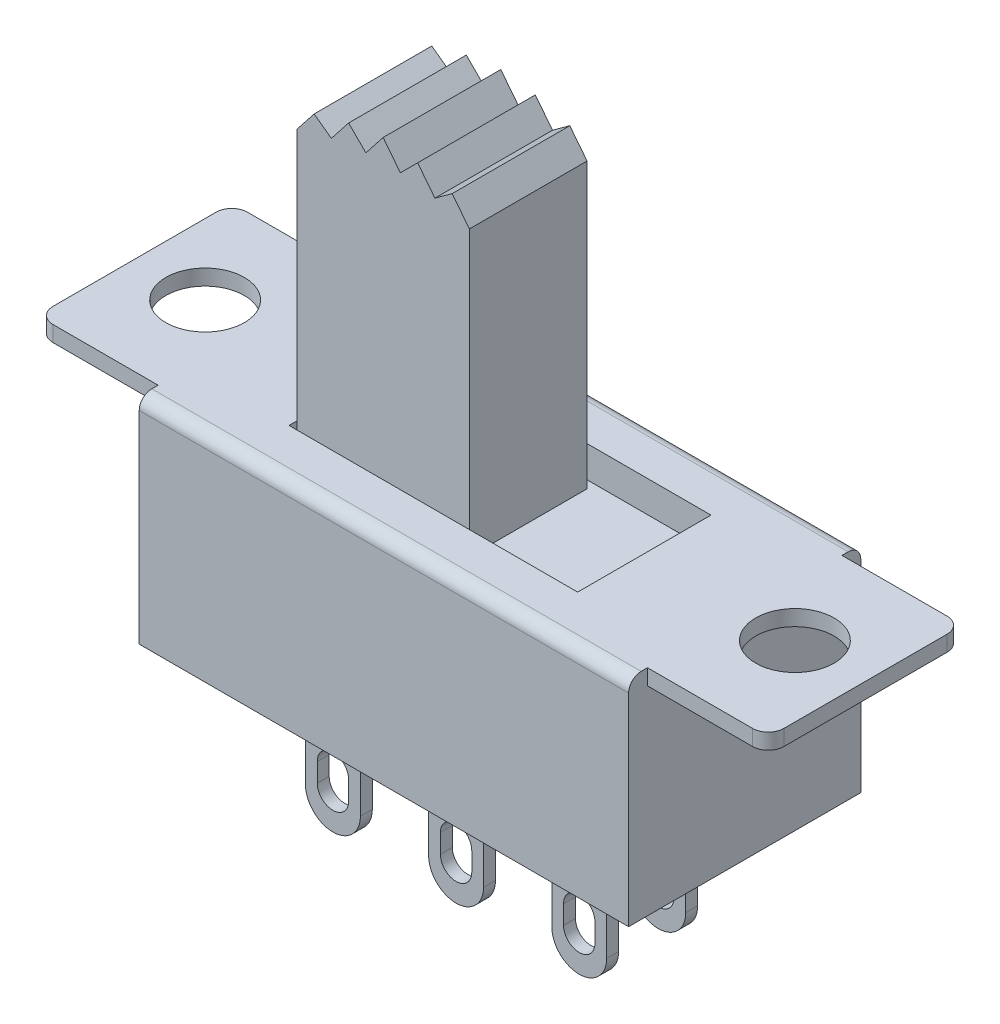
SolidWorks part; units mm, degrees
ref_plane "Plan de face" through (0, 0, 0) normal (0, 0, 1) x (1, 0, 0)
ref_plane "Plan de dessus" through (0, 0, 0) normal (0, 1, 0) x (1, 0, 0)
ref_plane "Plan de droite" through (0, 0, 0) normal (1, 0, 0) x (0, 0, -1)
sketch "Esquisse1" plane through (0, 0, 0) normal (0, 1, 0) x (1, 0, 0)
  line L0 (7.8, 3.1) -> (11.65, 3.1)
  line L1 (-11.65, -3.1) -> (-7.8, -3.1)
  line L2 (-11.65, -3.1) -> (-11.65, 3.1)
  line L3 (-11.65, 3.1) -> (-7.8, 3.1)
  line L4 (11.65, -3.1) -> (11.65, 3.1)
  line L5 (-11.65, -3.1) -> (11.65, 3.1) construction
  line L6 (-11.65, 3.1) -> (11.65, -3.1) construction
  line L7 (-7.8, -3.7) -> (7.8, -3.7)
  line L8 (-7.8, -3.7) -> (-7.8, -3.1)
  line L9 (-7.8, 3.7) -> (7.8, 3.7)
  line L10 (7.8, -3.7) -> (7.8, -3.1)
  line L11 (-7.8, -3.7) -> (7.8, 3.7) construction
  line L12 (-7.8, 3.7) -> (7.8, -3.7) construction
  line L13 (7.8, -3.1) -> (11.65, -3.1)
  line L14 (-7.8, 3.1) -> (-7.8, 3.7)
  line L15 (7.8, 3.1) -> (7.8, 3.7)
  line L16 (-7.8, 3.1) -> (-7.8, -3.1)
  line L17 (7.8, 3.1) -> (7.8, -3.1)
  line L19 (7.8, -3.7) -> (-7.8, -3.7)
  line L20 (7.8, -3.7) -> (7.8, 3.7)
  line L21 (7.8, 3.7) -> (-7.8, 3.7)
  line L22 (-7.8, -3.7) -> (-7.8, 3.7)
  line L23 (7.8, -3.7) -> (-7.8, 3.7) construction
  line L24 (7.8, 3.7) -> (-7.8, -3.7) construction
  circle A0 centre (-9.4, 0) radius 1.25
  circle A1 centre (9.4, 0) radius 1.25
  point P0 (0, 0)
  point P6 (0, 0)
  point P14 (0, 0)
  point P18 (-10.65, 0)
  point P21 (10.65, 0)
  dimension "D5" = 2.5
  dimension "D7" = 2.5
  dimension "D1" = 23.3
  dimension "D2" = 6.2
  dimension "D3" = 15.6
  dimension "D4" = 7.4
  dimension "D6" = 1
  dimension "D8" = 1
extrude "Plaque" add sketch "Esquisse1" against normal blind 0.5 contours L16 L3 L2 L1 A0 | L0 L17 L13 L4 A1 region at (9.725, 0, -3.027) region at (-7.873, 0, 0)
extrude "Corps" add sketch "Esquisse1<5>" against normal blind 6.85 contours L17 L15 L9 L14 L16 L8 L7 L10 region at (0, 0, 0)
sketch "Esquisse1<5>" plane through (0, 0, 0) normal (0, 1, 0) x (1, 0, 0) same geometry as "Esquisse1"
fillet "Congé" radius 0.5 4 edges at (-11.65, -0.25, -3.1) (11.65, -0.25, -3.1) (11.65, -0.25, 3.1) (-11.65, -0.25, 3.1)
sketch "Esquisse2" plane through (0, 0, 0) normal (0, 1, 0) x (1, 0, 0)
  line L1 (-4.6, -2.125) -> (4.6, -2.125)
  line L2 (-4.6, -2.125) -> (-4.6, 2.125)
  line L3 (-4.6, 2.125) -> (4.6, 2.125)
  line L4 (4.6, -2.125) -> (4.6, 2.125)
  line L5 (-4.6, -2.125) -> (4.6, 2.125) construction
  line L6 (-4.6, 2.125) -> (4.6, -2.125) construction
  point P0 (0, 0)
  dimension "D1" = 4.25
  dimension "D2" = 9.2
extrude "Cavité" cut sketch "Esquisse2" against normal blind 1
sketch "Esquisse3" plane through (0, -1, 0) normal (0, 1, 0) x (1, 0, 0)
  line L2 (-4.6, 2.125) -> (-4.6, -2.125) construction
  line L3 (-4.6, -1.875) -> (0.9, -1.875)
  line L4 (-4.6, -1.875) -> (-4.6, 1.875)
  line L5 (-4.6, 1.875) -> (0.9, 1.875)
  line L6 (0.9, -1.875) -> (0.9, 1.875)
  line L7 (-4.6, -1.875) -> (0.9, 1.875) construction
  line L8 (-4.6, 1.875) -> (0.9, -1.875) construction
  point P4 (-1.85, 0)
  dimension "D1" = 3.75
  dimension "D2" = 5.5
extrude "Bouton" add sketch "Esquisse3" along normal blind 10.2
sketch "Esquisse5" plane through (0, 0, 1.875) normal (0, 0, 1) x (1, 0, 0)
  line L0 (-4.6, 8.05) -> (-4.05, 8.75)
  line L1 (-4.6, 9.2) -> (-4.6, 0) construction
  line L2 (-4.05, 8.75) -> (-3.5, 8.35)
  line L3 (-3.5, 8.35) -> (-2.95, 9.05)
  line L4 (-2.95, 9.05) -> (-2.4, 8.5)
  line L5 (-2.4, 8.5) -> (-1.85, 9.2)
  line L6 (-4.6, 9.2) -> (0.9, 9.2) construction
  line L7 (-1.85, 9.2) -> (-1.3, 8.5)
  line L8 (-1.3, 8.5) -> (-0.75, 9.05)
  line L9 (-0.75, 9.05) -> (-0.2, 8.35)
  line L10 (-0.2, 8.35) -> (0.35, 8.75)
  line L11 (0.35, 8.75) -> (0.9, 8.05)
  line L12 (0.9, 9.2) -> (0.9, -1) construction
  line L13 (-4.6, 8.05) -> (-4.6, 9.2)
  line L14 (-7.8, 0) -> (7.8, 0) construction
  line L15 (-4.6, 9.2) -> (0.9, 9.2)
  line L16 (0.9, 9.2) -> (0.9, 8.05)
  line M3 (0.9, -1) -> (0.9, 9.2)
  line M4 (0.9, 9.2) -> (-4.6, 9.2)
  line M5 (-4.6, 9.2) -> (-4.6, 0)
  dimension "D1" = 0.55
  dimension "D2" = 0.55
  dimension "D3" = 1.1
  dimension "D4" = 1.1
  dimension "D5" = 0.7
  dimension "D6" = 9.05
  dimension "D7" = 8.75
  dimension "D8" = 0.7
  dimension "D9" = 0.7
  dimension "D10" = 0.55
  dimension "D11" = 1.1
  dimension "D12" = 1.1
  dimension "D13" = 0.55
extrude "Relief" cut sketch "Esquisse5" against normal through all contours L4 L5 L0 L2 L3 M4 M5 | L10 L11 L7 L8 L9 M3 M4 region at (-3.4714, 8.874, 1.875) region at (-0.2286, 8.874, 1.875)
fillet "Congé2" radius 0.4 2 edges at (0, 0, 3.7) (0, 0, -3.7)
sketch "Esquisse6" plane through (0, -6.85, 0) normal (0, -1, 0) x (1, 0, 0)
  line L5 (-7.8, 3.7) -> (7.8, 3.7) construction
  line L13 (-5, 1.4) -> (-2.85, 1.4)
  line L14 (-5, 1.4) -> (-5, 1.02)
  line L15 (-5, 1.02) -> (-2.85, 1.02)
  line L16 (-2.85, 1.4) -> (-2.85, 1.02)
  line L17 (-7.8, 3.7) -> (-7.8, -3.7) construction
  dimension "D1" = 2.3
  dimension "D2" = 0.38
  dimension "D7" = 2.8
  dimension "D8" = 2.15
extrude "Pin" add sketch "Esquisse6" along normal blind 4.4
sketch "Esquisse8" plane through (0, 0, 1.4) normal (0, 0, 1) x (1, 0, 0)
  line L0 (-5, -6.85) -> (-5, -7.15)
  line L1 (-5, -11.25) -> (-5, -6.85) construction
  line L2 (-5, -7.15) -> (-4.8, -7.45)
  line L3 (-4.8, -7.45) -> (-4.8, -10.375)
  line L4 (-3.05, -10.375) -> (-3.05, -7.45)
  line L5 (-3.05, -7.45) -> (-2.85, -7.15)
  line L6 (-2.85, -11.25) -> (-2.85, -6.85) construction
  line L7 (-2.85, -7.15) -> (-2.85, -6.85)
  line L8 (-2.85, -6.85) -> (-5, -6.85)
  line L9 (-2.85, -11.25) -> (-5, -11.25) construction
  line L10 (-5, -7.15) -> (-5, -11.25)
  line L11 (-5, -11.25) -> (-2.85, -11.25)
  line L12 (-2.85, -11.25) -> (-2.85, -7.15)
  line L14 (-5, -6.85) -> (-2.85, -6.85)
  line L15 (-5, -6.85) -> (-5, -11.25)
  line L16 (-5, -11.25) -> (-2.85, -11.25)
  line L17 (-2.85, -6.85) -> (-2.85, -11.25)
  arc A0 (-4.8, -10.375) -> (-3.05, -10.375) centre (-3.925, -10.375) ccw
  point P9 (-3.925, -11.25)
  point P18 (-3.925, -11.25)
  line M10 (-5, -6.85) -> (-5, -11.25)
  line M11 (-5, -11.25) -> (-2.85, -11.25)
  line M12 (-2.85, -11.25) -> (-2.85, -6.85)
  dimension "D1" = 1.75
  dimension "D2" = 0.6
  dimension "D3" = 0.3
extrude "Arrondi" cut sketch "Esquisse8" against normal up to surface (0.38 mm away) contours A0 L3 L2 M10 M11 | A0 L16 L5 L4 M12 region at (-4.8502, -9.5806, 1.4) region at (-2.9998, -9.5806, 1.4) up to face at (-3.925, -9.05, 1.02)
sketch "Esquisse9" plane through (0, 0, 1.4) normal (0, 0, 1) x (1, 0, 0)
  line L0 (-3.925, -10.15) -> (-3.925, -9.55) construction
  line L1 (-4.425, -10.15) -> (-4.425, -9.55)
  line L2 (-3.425, -10.15) -> (-3.425, -9.55)
  arc A0 (-4.425, -10.15) -> (-3.425, -10.15) centre (-3.925, -10.15) ccw
  arc A1 (-3.425, -9.55) -> (-4.425, -9.55) centre (-3.925, -9.55) ccw
  arc A3 (-4.8, -10.375) -> (-3.05, -10.375) centre (-3.925, -10.375) ccw construction
  point P2 (-3.925, -9.85)
  point P7 (-3.925, -10.65)
  point P8 (-3.925, -9.05)
  point P14 (-3.925, -11.25)
  dimension "D1" = 1
  dimension "D2" = 1.6
  dimension "D3" = 0.6
extrude "Percage" cut sketch "Esquisse9" against normal up to surface (0.38 mm away) up to face at (-3.925, -8.0656, 1.02)
pattern_linear "Répétition" count 3 spacing 3.925 along (1, 0, 0) count 2 spacing 2.52 along (0, 0, -1) of "Pin", "Arrondi", "Percage"
